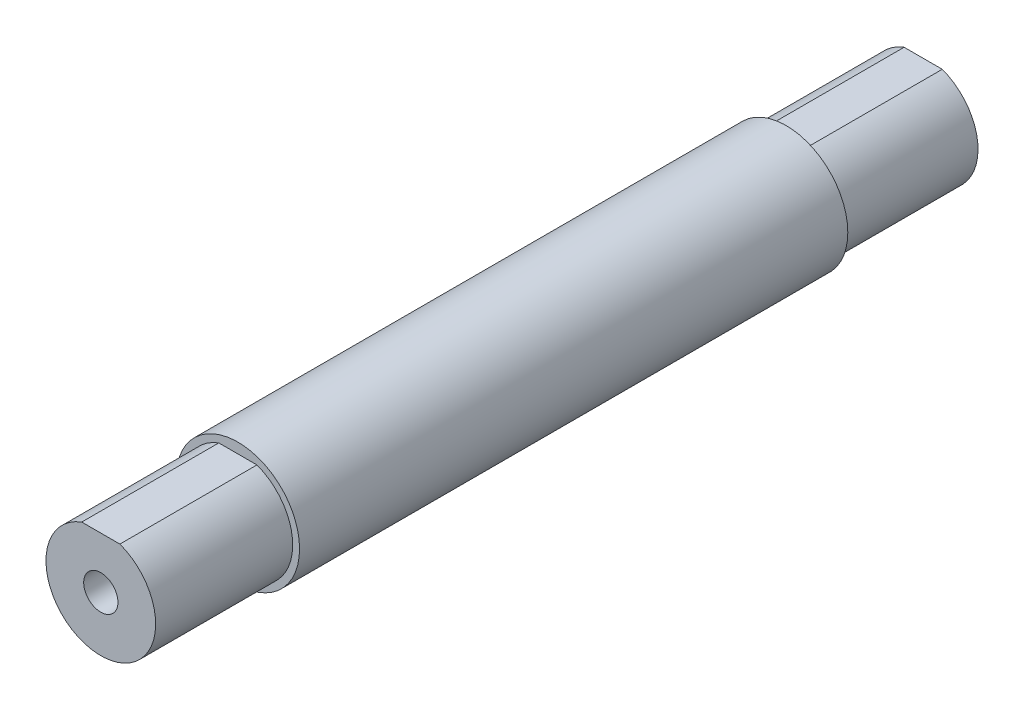
SolidWorks part; units mm, degrees
material "普通碳钢"
ref_plane "前视基准面" through (0, 0, 0) normal (0, 0, 1) x (1, 0, 0)
ref_plane "上视基准面" through (0, 0, 0) normal (0, 1, 0) x (1, 0, 0)
ref_plane "右视基准面" through (0, 0, 0) normal (1, 0, 0) x (0, 0, -1)
sketch "草图1" plane through (0, 0, 0) normal (0, 0, 1) x (1, 0, 0)
  line L0 (-87.1056, 0) -> (87.1056, 0) construction
  line L1 (0, 87.1056) -> (0, -87.1056) construction
  line L2 (-2.7839, 7.5) -> (2.7839, 7.5)
  circle A0 centre (0, 0) radius 9
  circle A1 centre (0, 0) radius 8
  dimension "D1" = 18
  dimension "D2" = 16
  dimension "D3" = 7.5
extrude "凸台-拉伸1" add sketch "草图1" along normal mid plane 120 contours A1 region at (0, -0.0722, 0)
extrude "凸台-拉伸2" add sketch "草图1<3>" along normal mid plane 80 contours A0 A1 | L2 A1 region at (0, 7.7005, 0) region at (-8.7454, 0, 0)
sketch "草图1<3>" plane through (0, 0, 0) normal (0, 0, 1) x (1, 0, 0) same geometry as "草图1"
hole_wizard "M6 螺纹孔1" positions "草图5" profile "草图4" tap size "M6" standard "GB"
sketch "草图5" plane through (0, 0, 60) normal (0, 0, 1) x (1, 0, 0)
  point P0 (0, 0)
sketch "草图4" plane through (0, 0, 60) normal (1, 0, 0) x (0, -1, 0)
  line L0 (0, 0) -> (0, 19.5022)
  line L1 (0, 19.5022) -> (2.5, 18)
  line L2 (2.5, 18) -> (2.5, 0)
  line L5 (2.5, 0) -> (0, 0)
  line L10 (0, 19.5022) -> (-2.5, 18) construction
  line L11 (0, -6.35) -> (0, 107.95) construction
  dimension "螺纹孔钻头直径" = 5
  dimension "螺纹孔钻头深度" = 18
  dimension "导头角度" = 118
cosmetic thread "孔螺蚊线1" parameters "D1"=15, "D2"=6
mirror "镜向1" about plane through (0, 0, 0) normal (0, 0, 1) of "M6 螺纹孔1"
